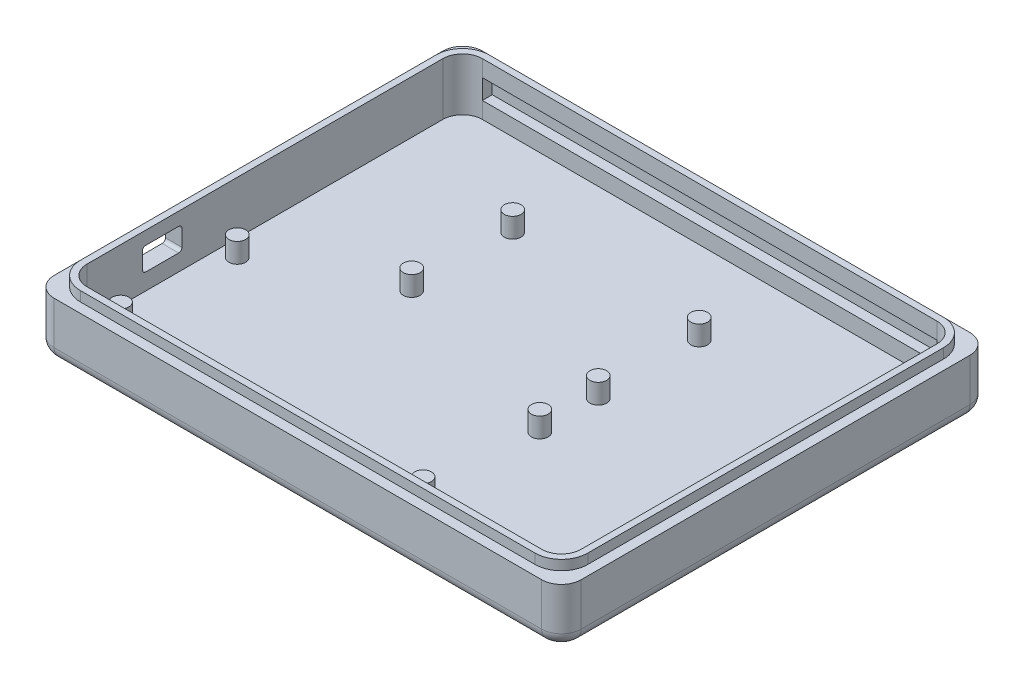
SolidWorks part; units mm, degrees
ref_plane "Front Plane" through (0, 0, 0) normal (0, 0, 1) x (1, 0, 0)
ref_plane "Top Plane" through (0, 0, 0) normal (0, 1, 0) x (1, 0, 0)
ref_plane "Right Plane" through (0, 0, 0) normal (1, 0, 0) x (0, 0, -1)
sketch "Sketch1" plane through (0, 0, 0) normal (0, 1, 0) x (1, 0, 0)
  line L0 (0, 0) -> (80, 0)
  line L1 (80, 0) -> (80, 65)
  line L2 (80, 65) -> (0, 65)
  line L3 (0, 65) -> (0, 0)
  dimension "D1" = 80
  dimension "D2" = 65
extrude "Boss-Extrude1" add sketch "Sketch1" along normal blind 10
sketch "Sketch2" plane through (0, 10, 0) normal (0, 1, 0) x (1, 0, 0)
  line L0 (0, 0) -> (77.5, 0)
  line L1 (0, 0) -> (80, 0) construction
  line L2 (77.5, 0) -> (77.5, 62.5)
  line L3 (77.5, 62.5) -> (2.5, 62.5)
  line L4 (2.5, 62.5) -> (2.5, 0)
  line L5 (2.5, 2.5) -> (77.5, 2.5)
  line L6 (0, 65) -> (0, 0) construction
  dimension "D1" = 60
  dimension "D2" = 75
  dimension "D3" = 2.5
  dimension "D4" = 2.5
extrude "Cut-Extrude1" cut sketch "Sketch2" along direction (0, 1, 0) on the side against the normal blind 8 contours L4 L5 L2 L3 region at (40, 10, -32.5)
fillet "Fillet4" radius 2 4 edges at (0, 0, -32.5) (40, 0, 0) (80, 0, -32.5) (40, 0, -65)
fillet "Fillet5" radius 3 12 edges at (79.4142, 0.5858, -0.5858) (79.4142, 0.5858, -64.4142) (0.5858, 0.5858, -64.4142) (0.5858, 0.5858, -0.5858) (80, 6, 0) (80, 6, -65) (0, 6, -65) (0, 6, 0) (2.5, 6, -2.5) (77.5, 6, -2.5) (77.5, 6, -62.5) (2.5, 6, -62.5)
sketch "Sketch3" plane through (0, 10, 0) normal (0, 1, 0) x (1, 0, 0)
  line L0 (0, 0) -> (80, 0)
  line L1 (80, 0) -> (80, 65)
  line L2 (80, 65) -> (0, 65)
  line L3 (0, 65) -> (0, 0)
  line L4 (1.5, 63.5) -> (1.5, 1.5)
  line L5 (1.5, 1.5) -> (78.5, 1.5)
  line L6 (78.5, 1.5) -> (78.5, 63.5)
  line L7 (78.5, 63.5) -> (1.5, 63.5)
  dimension "D1" = 65
  dimension "D2" = 1.5
extrude "Cut-Extrude2" cut sketch "Sketch3" against normal blind 1.5
fillet "Fillet7" radius 4 4 edges at (1.5, 9.25, -63.5) (1.5, 9.25, -1.5) (78.5, 9.25, -1.5) (78.5, 9.25, -63.5)
sketch "Sketch4" plane through (0, 2, 0) normal (0, 1, 0) x (1, 0, 0)
  line L0 (0, 62) -> (0, 3) construction
  line L1 (3, 0) -> (77, 0) construction
  line L2 (77, 65) -> (3, 65) construction
  circle A0 centre (5.04, 8.04) radius 1.27
  circle A1 centre (5.04, 25.76) radius 1.27
  circle A2 centre (22.64, 34.64) radius 1.27
  circle A3 centre (22.64, 49.96) radius 1.27
  circle A4 centre (50.96, 8.04) radius 1.27
  circle A5 centre (50.96, 25.76) radius 1.27
  circle A8 centre (50.96, 34.64) radius 1.27
  circle A9 centre (50.96, 49.96) radius 1.27
  dimension "D1" = 2.54
  dimension "D4" = 2.54
  dimension "D5" = 2.54
  dimension "D6" = 2.54
  dimension "D11" = 50.96
  dimension "D2" = 5.04
  dimension "D3" = 8.04
  dimension "D7" = 17.72
  dimension "D8" = 15.04
  dimension "D9" = 15.32
  dimension "D13" = 28.32
  dimension "D10" = 2
  dimension "D12" = 2
extrude "Boss-Extrude2" add sketch "Sketch4" along normal blind 3
sketch "Sketch5" plane through (2.5, 0, 0) normal (1, 0, 0) x (0, 0, -1)
  line L0 (13.9, 4.5) -> (13.9, 8)
  line L3 (19.9, 8) -> (19.9, 4.5)
  line L4 (19.9, 4.5) -> (13.9, 4.5)
  line L5 (2.5, 2) -> (2.5, 10) construction
  line L6 (19.9, 8) -> (13.9, 8)
  line L7 (59.5, 10) -> (5.5, 10) construction
  dimension "D1" = 11.4
  dimension "D2" = 6
  dimension "D3" = 5.5
  dimension "D4" = 3.5
extrude "Cut-Extrude3" cut sketch "Sketch5" against normal through all
fillet "Fillet8" radius 0.5 4 edges at (1.25, 4.5, -13.9) (1.25, 4.5, -19.9) (1.25, 8, -13.9) (1.25, 8, -19.9)
sketch "Sketch8" plane through (0, 0, -62.5) normal (0, 0, 1) x (1, 0, 0)
  line L0 (5.5, 7.5) -> (74.5, 7.5)
  line L1 (5.5, 10) -> (5.5, 2) construction
  line L2 (74.5, 2) -> (74.5, 10) construction
  line L3 (74.5, 7.5) -> (74.5, 4.5)
  line L4 (74.5, 4.5) -> (5.5, 4.5)
  line L5 (5.5, 4.5) -> (5.5, 7.5)
  line L6 (74.5, 10) -> (5.5, 10) construction
  dimension "D1" = 2.5
  dimension "D2" = 3
extrude "Cut-Extrude4" cut sketch "Sketch8" against normal blind 1.5
sketch "Sketch9" plane through (0, 0, -2.5) normal (0, 0, -1) x (-1, 0, 0)
  line L0 (-74.5, 7.5) -> (-5.5, 7.5)
  line L1 (-74.5, 10) -> (-74.5, 2) construction
  line L2 (-5.5, 2) -> (-5.5, 10) construction
  line L3 (-5.5, 7.5) -> (-5.5, 4.5)
  line L4 (-5.5, 4.5) -> (-74.5, 4.5)
  line L5 (-74.5, 4.5) -> (-74.5, 7.5)
  line L6 (-5.5, 10) -> (-74.5, 10) construction
  dimension "D1" = 2.5
  dimension "D2" = 3
extrude "Cut-Extrude5" cut sketch "Sketch9" against normal blind 1.5
